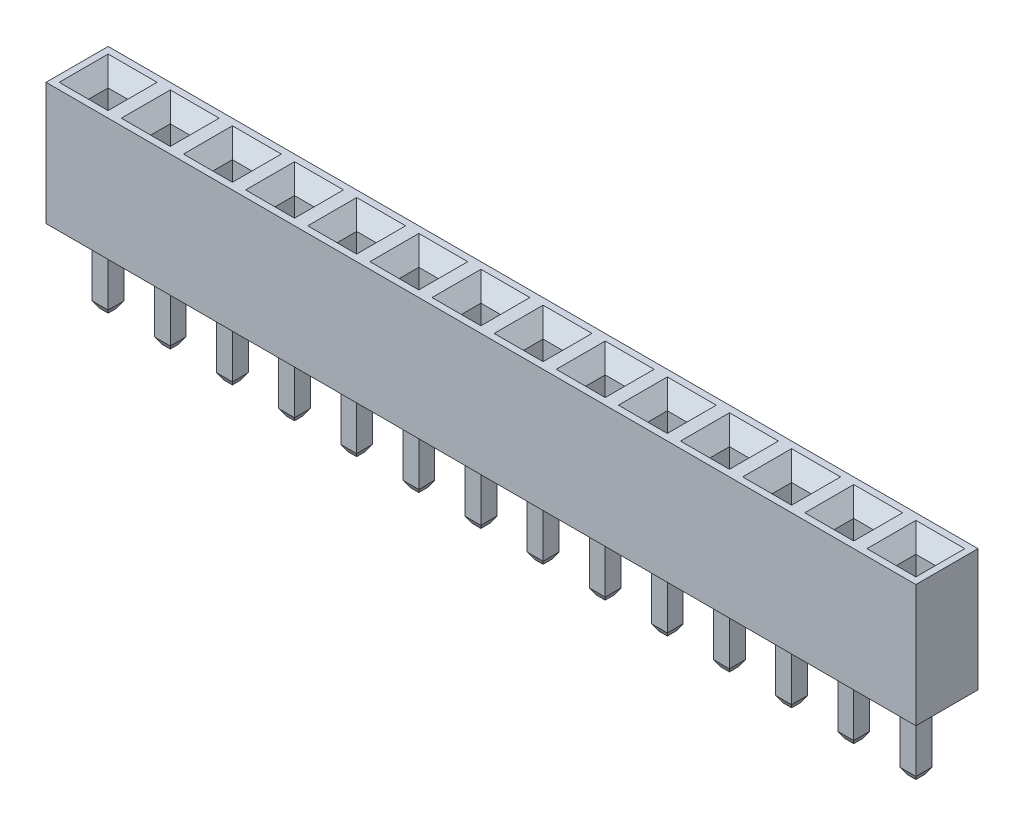
SolidWorks part; units mm, degrees
ref_plane "Front Plane" through (0, 0, 0) normal (0, 0, 1) x (1, 0, 0)
ref_plane "Top Plane" through (0, 0, 0) normal (0, 1, 0) x (1, 0, 0)
ref_plane "Right Plane" through (0, 0, 0) normal (1, 0, 0) x (0, 0, -1)
sketch "Sketch1" plane through (0, 0, 0) normal (0, 1, 0) x (1, 0, 0)
  line L1 (-1.27, 1.27) -> (1.27, 1.27)
  line L2 (-1.27, 1.27) -> (-1.27, -1.27)
  line L3 (-1.27, -1.27) -> (1.27, -1.27)
  line L4 (1.27, 1.27) -> (1.27, -1.27)
  line L5 (-1.27, 1.27) -> (1.27, -1.27) construction
  line L6 (-1.27, -1.27) -> (1.27, 1.27) construction
  point P0 (0, 0)
  dimension "D1" = 2.54
extrude "Boss-Extrude1" add sketch "Sketch1" along normal blind 5
sketch "Sketch2" plane through (0, 0, 0) normal (0, -1, 0) x (1, 0, 0)
  line L1 (-0.325, 0.325) -> (0.325, 0.325)
  line L2 (-0.325, 0.325) -> (-0.325, -0.325)
  line L3 (-0.325, -0.325) -> (0.325, -0.325)
  line L4 (0.325, 0.325) -> (0.325, -0.325)
  line L5 (-0.325, 0.325) -> (0.325, -0.325) construction
  line L6 (-0.325, -0.325) -> (0.325, 0.325) construction
  point P0 (0, 0)
  dimension "D1" = 0.65
extrude "Boss-Extrude2" add sketch "Sketch2" along normal blind 3
chamfer "Chamfer1" distance 0.15 angle 60 4 edges at (0, -3, -0.325) (-0.325, -3, 0) (0, -3, 0.325) (0.325, -3, 0) first distance on face at (0, -3, 0)
sketch "Sketch3" plane through (0, 5, 0) normal (0, 1, 0) x (1, 0, 0)
  line L1 (-0.4, 0.4) -> (0.4, 0.4)
  line L2 (-0.4, 0.4) -> (-0.4, -0.4)
  line L3 (-0.4, -0.4) -> (0.4, -0.4)
  line L4 (0.4, 0.4) -> (0.4, -0.4)
  line L5 (-0.4, 0.4) -> (0.4, -0.4) construction
  line L6 (-0.4, -0.4) -> (0.4, 0.4) construction
  point P0 (0, 0)
  dimension "D1" = 0.8
extrude "Cut-Extrude1" cut sketch "Sketch3" against normal blind 3
chamfer "Chamfer2" distance 0.6 angle 45 4 edges at (-0.4, 5, 0) (0, 5, 0.4) (0.4, 5, 0) (0, 5, -0.4)
pattern_linear "LPattern1" count 14 spacing 2.54 along (1, 0, 0) of "Boss-Extrude1", "Boss-Extrude2", "Cut-Extrude1", "Chamfer2", "Chamfer1"
ref_axis "Axis1" through (0, -5.675, 0) along (0, 1, 0)
